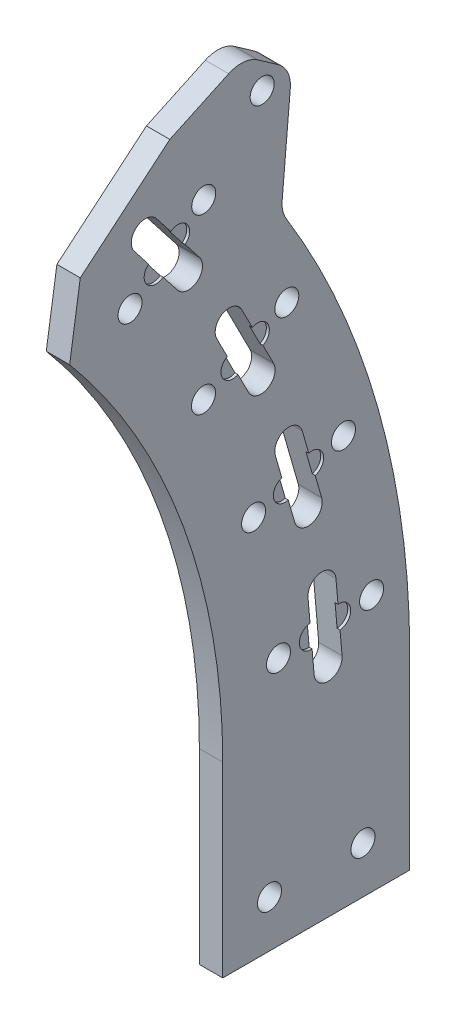
SolidWorks part; units mm, degrees
material "6061-T6 (SS)"
ref_plane "Front Plane" through (0, 0, 0) normal (0, 0, 1) x (1, 0, 0)
ref_plane "Top Plane" through (0, 0, 0) normal (0, 1, 0) x (1, 0, 0)
ref_plane "Right Plane" through (0, 0, 0) normal (1, 0, 0) x (0, 0, -1)
sketch "Sketch1" plane through (0, 0, 0) normal (1, 0, 0) x (0, 0, -1)
  line L0 (0, 0) -> (177.8, 0) construction
  line L1 (0, 0) -> (136.2027, 114.2876) construction
  line L2 (177.8, 0) -> (177.8, -50.8)
  line L3 (177.8, -50.8) -> (228.6, -50.8)
  line L4 (228.6, -50.8) -> (228.6, 0)
  line L5 (136.2027, 114.2876) -> (175.1178, 146.9412) construction
  line L6 (177.8, 0) -> (228.6, 0) construction
  line L7 (136.2027, 114.2876) -> (175.1178, 146.9412) construction
  line L9 (0, 0) -> (0, 168.3639) construction
  line L28 (177.8, -50.8) -> (177.8, -38.1) construction
  line L29 (177.8, -38.1) -> (228.6, -38.1) construction
  line L30 (0, 0) -> (136.2027, 114.2876) construction
  line L33 (175.1178, 146.9412) -> (163.4134, 153.6988)
  line L34 (163.4134, 153.6988) -> (139.0915, 133.2903)
  line L35 (139.0915, 133.2903) -> (136.2027, 114.2876)
  arc A0 (177.8, 0) -> (136.2027, 114.2876) centre (0, 0) ccw
  arc A1 (228.6, 0) -> (175.1178, 146.9412) centre (0, 0) ccw
  circle A32 centre (190.5, -38.1) radius 3.2639
  circle A33 centre (215.9, -38.1) radius 3.2639
  point P11 (151.8201, 13.2825)
  point P24 (175.0988, 30.8746)
  dimension "D24" = 6.5278
  dimension "D25" = 6.5278
  dimension "D1" = 177.8
  dimension "D2" = 40
  dimension "D3" = 50.8
  dimension "D4" = 50.8
  dimension "D10" = 90
  dimension "D21" = 12.7
  dimension "D22" = 12.7
  dimension "D23" = 12.7
  dimension "D28" = 12.7
  dimension "D29" = 31.75
  dimension "D30" = 110
extrude "Boss-Extrude1" add sketch "Sketch1" along normal blind 6.35
sketch "Sketch5" plane through (0, 0, 0) normal (0, 0, 1) x (1, 0, 0)
  line L0 (-1000, 0) -> (49000, 0) construction
sketch "Sketch6" plane through (6.35, 0, 0) normal (1, 0, 0) x (0, 0, -1)
  line L0 (0, 0) -> (203.2, 0) construction
  line L1 (0, 0) -> (155.6602, 130.6144) construction
  line L2 (0, 0) -> (218.2414, 19.0936) construction
  line L3 (0, 0) -> (210.5884, 60.3853) construction
  line L4 (0, 0) -> (195.1973, 99.458) construction
  line L5 (0, 0) -> (172.6335, 134.876) construction
  line L6 (192.0925, 64.9905) -> (197.3434, 46.6785)
  line L7 (176.1625, 100.4494) -> (184.811, 83.4757)
  line L8 (0, 0) -> (192.938, 16.8799) construction
  line L9 (0, 0) -> (186.1724, 53.3841) construction
  line L10 (200.964, 27.1435) -> (202.6243, 8.1659)
  line L11 (208.555, 27.8076) -> (210.2153, 8.8301)
  line L12 (200.964, 27.1435) -> (208.555, 27.8076) construction
  line L13 (210.2153, 8.8301) -> (202.6243, 8.1659) construction
  line L14 (204.6682, 48.7788) -> (197.3434, 46.6785) construction
  line L16 (192.0925, 64.9905) -> (199.4173, 67.0909) construction
  line L17 (199.4173, 67.0909) -> (204.6682, 48.7788)
  line L18 (191.6005, 86.9352) -> (184.811, 83.4757) construction
  line L20 (176.1625, 100.4494) -> (182.9519, 103.9088) construction
  line L21 (182.9519, 103.9088) -> (191.6005, 86.9352)
  line L22 (171.4922, 121.897) -> (165.4876, 117.2057) construction
  line L24 (153.7592, 132.2173) -> (159.7639, 136.9086) construction
  line L25 (159.7639, 136.9086) -> (171.4922, 121.897)
  line L30 (192.0925, 64.9905) -> (197.3434, 46.6785) [skipped]
  line L31 (176.1625, 100.4494) -> (184.811, 83.4757) [skipped]
  line L33 (153.7592, 132.2173) -> (165.4876, 117.2057) [skipped]
  line L34 (153.7592, 132.2173) -> (165.4876, 117.2057)
  arc A0 (203.2, 0) -> (155.6602, 130.6144) centre (0, 0) ccw construction
  arc A1 (209.55, 0) -> (160.5246, 134.6961) centre (0, 0) ccw construction
  circle A2 centre (218.2414, 19.0936) radius 9.525 construction
  arc A3 (228.6, 0) -> (175.1178, 146.9412) centre (0, 0) ccw construction
  circle A4 centre (192.938, 16.8799) radius 9.525 construction
  circle A5 centre (192.938, 16.8799) radius 3.2639
  circle A6 centre (218.2414, 19.0936) radius 3.2639
  circle A7 centre (186.1724, 53.3841) radius 3.2639
  circle A8 centre (186.1724, 53.3841) radius 9.525 construction
  circle A9 centre (210.5884, 60.3853) radius 3.2639
  circle A10 centre (210.5884, 60.3853) radius 9.525 construction
  circle A11 centre (172.5657, 87.9266) radius 3.2639
  circle A12 centre (172.5657, 87.9266) radius 9.525 construction
  circle A13 centre (195.1973, 99.458) radius 3.2639
  circle A14 centre (195.1973, 99.458) radius 9.525 construction
  circle A15 centre (152.618, 119.2382) radius 3.2639
  circle A16 centre (152.618, 119.2382) radius 9.525 construction
  circle A17 centre (172.6335, 134.876) radius 3.2639
  circle A18 centre (172.6335, 134.876) radius 9.525 construction
  arc A20 (199.4173, 67.0909) -> (192.0925, 64.9905) centre (195.7549, 66.0407) ccw
  arc A22 (191.6005, 86.9352) -> (184.811, 83.4757) centre (188.2057, 85.2055) cw
  arc A24 (208.555, 27.8076) -> (200.964, 27.1435) centre (204.7595, 27.4755) ccw
  arc A26 (210.2153, 8.8301) -> (202.6243, 8.1659) centre (206.4198, 8.498) cw
  arc A27 (204.6682, 48.7788) -> (197.3434, 46.6785) centre (201.0058, 47.7286) cw
  arc A28 (182.9519, 103.9088) -> (176.1625, 100.4494) centre (179.5572, 102.1791) ccw
  arc A29 (171.4922, 121.897) -> (165.4876, 117.2057) centre (168.4899, 119.5513) cw
  arc A30 (159.7639, 136.9086) -> (153.7592, 132.2173) centre (156.7615, 134.5629) ccw
  dimension "D3" = 19.05
  dimension "D4" = 19.05
  dimension "D6" = 6.5278
  dimension "D7" = 6.5278
  dimension "D13" = 8.89
  dimension "D2" = 40
  dimension "D5" = 5
  dimension "D9" = 11
  dimension "D10" = 19.05
  dimension "D11" = 9.525
  dimension "D1" = 6.35
  dimension "D12" = 7.62
  dimension "D8" = 4
extrude "Cut-Extrude1" cut sketch "Sketch6" against normal through all
sketch "Sketch8" plane through (6.35, 15.5516, -177.756) normal (1, 0, 0) x (0, 0.0872, -0.9962)
  line L0 (31.75, 0) -> (34.1312, 0) construction
  line L1 (31.75, -9.525) -> (31.75, 9.525) construction
  line L2 (31.75, 3.175) -> (24.13, 3.175)
  line L3 (24.13, 9.525) -> (24.13, -9.525) construction
  line L4 (24.13, -3.175) -> (31.75, -3.175)
  arc A1 (31.75, 3.175) -> (31.75, -3.175) centre (31.75, 0) cw
  arc A2 (24.13, 3.175) -> (24.13, -3.175) centre (24.13, 0) ccw
  dimension "D1" = 3.175
  dimension "D2" = 2.3812
extrude "Cut-Extrude2" cut sketch "Sketch8" against normal blind 0.7937 and the other way blind 10.033
pattern_circular "CirPattern1" count 4 every 11 about axis through (6.35, 0, 0) along (-1, 0, 0) of "Cut-Extrude2" reverse direction yes
sketch "Sketch9" plane through (6.35, 0, 0) normal (1, 0, 0) x (0, 0, -1)
  line L0 (0, 0) -> (188.5123, 152.6542) construction
  line L1 (0, 0) -> (72.4364, 0) construction
  circle A0 centre (188.5123, 152.6542) radius 3.2639
  dimension "D3" = 6.5278
  dimension "D1" = 242.57
  dimension "D2" = 39
sketch "Sketch11" plane through (6.35, 0, 0) normal (1, 0, 0) x (0, 0, -1)
  line L0 (163.4134, 153.6988) -> (183.5561, 163.0915)
  line L1 (183.5561, 163.0915) -> (196.5601, 153.9859)
  line L2 (196.5601, 153.9859) -> (193.7082, 121.3882)
  line L3 (163.4134, 153.6988) -> (139.0915, 133.2903) construction
  line L10 (139.0915, 133.2903) -> (136.2027, 114.2876)
  line L11 (177.8, 0) -> (177.8, -50.8)
  line L12 (177.8, -50.8) -> (228.6, -50.8)
  line L13 (228.6, -50.8) -> (228.6, 0)
  line L14 (175.1178, 146.9412) -> (163.4134, 153.6988)
  line L15 (163.4134, 153.6988) -> (139.0915, 133.2903)
  line L16 (139.0915, 133.2903) -> (136.2027, 114.2876)
  line L17 (177.8, 0) -> (177.8, -50.8)
  line L18 (177.8, -50.8) -> (228.6, -50.8)
  line L19 (228.6, -50.8) -> (228.6, 0)
  line L20 (175.1178, 146.9412) -> (163.4134, 153.6988)
  line L21 (163.4134, 153.6988) -> (139.0915, 133.2903)
  arc A0 (228.6, 0) -> (175.1178, 146.9412) centre (0, 0) ccw construction
  arc A7 (177.8, 0) -> (136.2027, 114.2876) centre (0, 0) ccw
  arc A8 (228.6, 0) -> (175.1178, 146.9412) centre (0, 0) ccw
  arc A12 (177.8, 0) -> (136.2027, 114.2876) centre (0, 0) ccw
  arc A13 (228.6, 0) -> (175.1178, 146.9412) centre (0, 0) ccw
  dimension "D1" = 165
  dimension "D2" = 22.225
  dimension "D3" = 15.875
  dimension "D4" = 120
  dimension "D5" = 120
  dimension "D6" = 0
extrude "Boss-Extrude2" add sketch "Sketch11" against normal blind 6.35 contours A13 L2 L1 L0 L20 region at (6.35, 147.1093, -184.7331)
extrude "Cut-Extrude3" cut sketch "Sketch9" against normal through all both and the other way through all
fillet "Fillet2" radius 7.9375 3 edges at (3.175, 153.9859, -196.5601) (3.175, 163.0915, -183.5561) (3.175, 121.3882, -193.7082)
